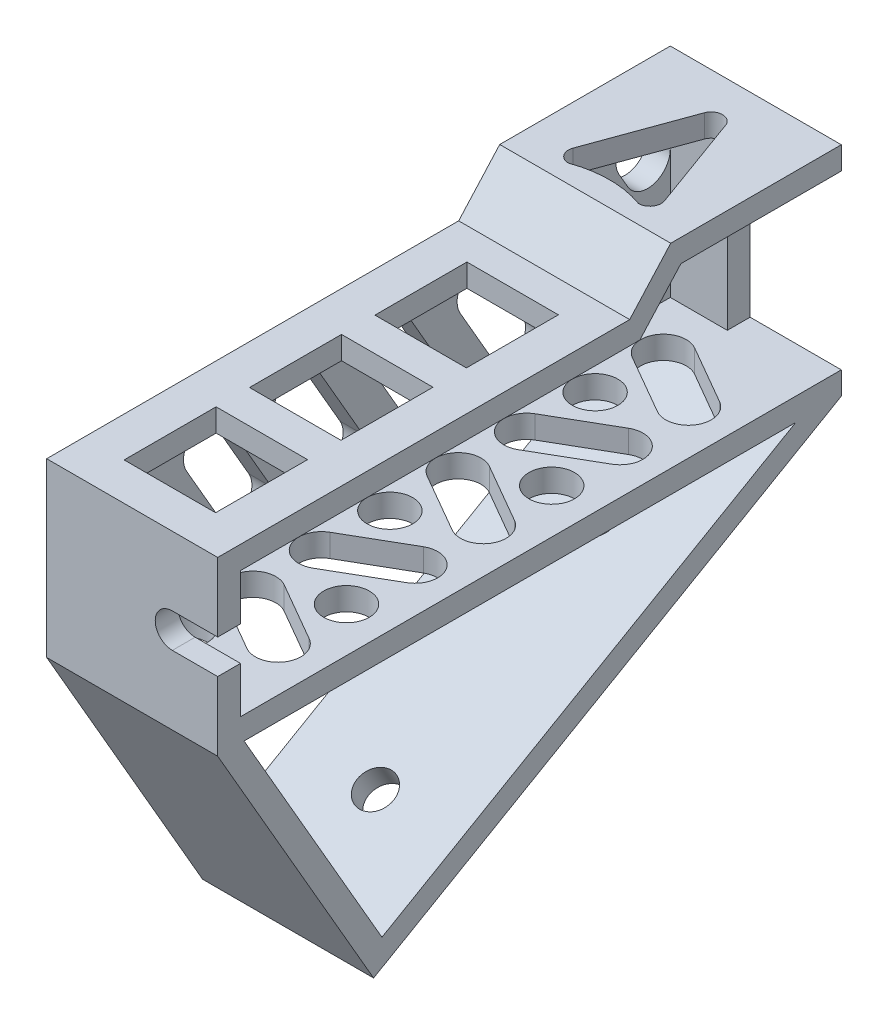
SolidWorks part; units mm, degrees
ref_plane "前视基准面" through (0, 0, 0) normal (0, 0, 1) x (1, 0, 0)
ref_plane "上视基准面" through (0, 0, 0) normal (0, 1, 0) x (1, 0, 0)
ref_plane "右视基准面" through (0, 0, 0) normal (1, 0, 0) x (0, 0, -1)
other "Configuration Table"
sketch "草图1" plane through (0, 0, 0) normal (1, 0, 0) x (0, 0, -1)
  line L0 (13.3, 15) -> (9.7, 11) construction
  line L1 (9.7, 11) -> (-25.3, 11) construction
  line L2 (-25.3, 11) -> (-25.3, 0) construction
  line L3 (-25.3, 0) -> (25.3, 0) construction
  line L4 (25.3, 0) -> (25.3, 15) construction
  line L5 (25.3, 15) -> (13.3, 15) construction
  line L12 (13.2777, 15.05) -> (9.6777, 11.05)
  line L13 (9.6777, 11.05) -> (-25.35, 11.05)
  line L14 (-25.35, 11.05) -> (-25.35, -0.05)
  line L15 (-25.35, -0.05) -> (25.35, -0.05)
  line L16 (25.35, -0.05) -> (25.35, 15.05)
  line L17 (25.35, 15.05) -> (13.2777, 15.05)
  line L18 (12.387, 17.05) -> (8.787, 13.05)
  line L19 (8.787, 13.05) -> (-27.35, 13.05)
  line L20 (-27.35, 13.05) -> (-27.35, -2.05)
  line L21 (-27.35, -2.05) -> (27.35, -2.05)
  line L22 (27.35, -2.05) -> (27.35, 17.05)
  line L23 (27.35, 17.05) -> (12.387, 17.05)
  point P7 (0, 0)
  dimension "D1" = 50.6
  dimension "D2" = 15
  dimension "D3" = 12
  dimension "D4" = 35
  dimension "D5" = 11
  dimension "D6" = 0.05
  dimension "D7" = 2
extrude "凸台-拉伸1" add sketch "草图1" along normal blind 15 contours L16 L17 L12 L13 L14 L15 | L12 L13 L14 L15 L16 L17 | L18 L19 L20 L21 L22 L23 region at (0, 6.1699, -1.6492)
extrude "凸台-拉伸2" add sketch "草图1<3>" along normal blind 2 contours L16 L17 L12 L13 L14 L15 region at (0, 6.1699, -1.6492)
sketch "草图1<3>" plane through (0, 0, 0) normal (1, 0, 0) x (0, 0, -1) same geometry as "草图1"
sketch "草图2" plane through (0, 0, 27.35) normal (0, 0, 1) x (1, 0, 0)
  line L0 (0, 5.5) -> (15, 5.5) construction
  line L1 (11.02, 7) -> (15, 7)
  line L2 (11.02, 4) -> (15, 4)
  line L4 (0, 13.05) -> (0, -2.05)
  line L5 (0, -2.05) -> (15, -2.05)
  line L6 (15, -2.05) -> (15, 13.05)
  line L7 (15, 13.05) -> (0, 13.05)
  line L8 (0, 13.05) -> (0, -2.05) construction
  line L9 (0, -2.05) -> (15, -2.05) construction
  line L10 (15, -2.05) -> (15, 13.05) construction
  line L11 (15, 13.05) -> (0, 13.05) construction
  circle A0 centre (11.02, 5.5) radius 1.5
  line M8 (15, -2.05) -> (15, 13.05)
  dimension "D2" = 3
  dimension "D3" = 11.02
  dimension "D1" = 0
extrude "切除-拉伸1" cut sketch "草图2" against normal up to next contours A0 | A0 L2 L1 M8 region at (13.579, 5.5, 27.35) region at (11.02, 5.5, 27.35)
sketch "草图3" plane through (0, 0, 0) normal (1, 0, 0) x (0, 0, -1)
  line L0 (27.35, -2.05) -> (-27.35, -2.05)
  line L2 (-13.675, -25.7358) -> (27.35, -2.05)
  line L3 (-12.9429, -23.0037) -> (23.35, -2.05)
  line L6 (-27.35, -2.05) -> (-13.675, -25.7358)
  line L7 (-25.0406, -2.05) -> (-12.9429, -23.0037)
  dimension "D1" = 30
  dimension "D2" = 2
  dimension "D3" = 2
extrude "凸台-拉伸3" add sketch "草图3" along normal blind 15 contours L0 L2 L3 region at (0, -13.3767, -6.5395)
sketch "草图4" plane through (0, 0, -27.35) normal (0, 0, -1) x (-1, 0, 0)
  line L0 (-7, 17.05) -> (-7, -2.05) construction
  line L2 (-15, 15.05) -> (-7, 15.05)
  line L3 (-15, 15.05) -> (-15, -0.05)
  line L4 (0, -2.05) -> (0, 17.05)
  line L5 (0, 17.05) -> (-15, 17.05)
  line L6 (-15, 17.05) -> (-15, -2.05)
  line L7 (-15, -2.05) -> (0, -2.05)
  line L8 (0, -2.05) -> (0, 17.05) construction
  line L9 (0, 17.05) -> (-15, 17.05) construction
  line L10 (-15, 17.05) -> (-15, -2.05) construction
  line L11 (-15, -2.05) -> (0, -2.05) construction
  line L12 (-15, -0.05) -> (-7, -0.05)
  line L13 (-7, 15.05) -> (-7, -0.05)
  line L14 (-15, 15.05) -> (-7, -0.05) construction
  line L15 (-15, -0.05) -> (-7, 15.05) construction
  point P10 (-11, 7.5)
  dimension "D2" = 7
  dimension "D3" = 2
  dimension "D4" = 2
  dimension "D1" = 0
extrude "切除-拉伸2" cut sketch "草图4" against normal up to next
sketch "草图5" plane through (0, -13.3804, -7.7252) normal (0, -0.866, -0.5) x (1, 0, 0)
  line L0 (7.5, 24.7108) -> (7.5, -22.6608) construction
  line L4 (0, 24.7108) -> (0, -22.6608)
  line L5 (0, -22.6608) -> (15, -22.6608)
  line L6 (15, -22.6608) -> (15, 24.7108)
  line L7 (15, 24.7108) -> (0, 24.7108)
  line L8 (0, 24.7108) -> (0, -22.6608) construction
  line L9 (0, -22.6608) -> (15, -22.6608) construction
  line L10 (15, -22.6608) -> (15, 24.7108) construction
  line L11 (15, 24.7108) -> (0, 24.7108) construction
  circle A0 centre (7.5, 14.7108) radius 1.6
  circle A1 centre (7.5, -7.6608) radius 1.6
  dimension "D2" = 3.2
  dimension "D4" = 3.2
  dimension "D3" = 10
  dimension "D5" = 15
  dimension "D1" = 0
extrude "切除-拉伸3" cut sketch "草图5" against normal up to next
sketch "草图6" plane through (0, 0, 0) normal (1, 0, 0) x (0, 0, -1)
  line L0 (-27.35, 5.5) -> (27.35, 5.5) construction
  line L1 (-23.35, 8.9641) -> (-19.35, 2.0359) construction
  line L2 (-21.6179, 9.9641) -> (-17.6179, 3.0359)
  line L3 (-25.0821, 7.9641) -> (-21.0821, 1.0359)
  line L4 (-15.35, 8.9641) -> (-11.35, 2.0359) construction
  line L5 (-13.6179, 9.9641) -> (-9.6179, 3.0359)
  line L6 (-17.0821, 7.9641) -> (-13.0821, 1.0359)
  line L7 (-7.35, 8.9641) -> (-3.35, 2.0359) construction
  line L8 (-5.6179, 9.9641) -> (-1.6179, 3.0359)
  line L9 (-9.0821, 7.9641) -> (-5.0821, 1.0359)
  line L10 (0.65, 8.9641) -> (4.65, 2.0359) construction
  line L11 (2.3821, 9.9641) -> (6.3821, 3.0359)
  line L12 (-1.0821, 7.9641) -> (2.9179, 1.0359)
  line L13 (8.65, 8.9641) -> (12.65, 2.0359) construction
  line L14 (10.3821, 9.9641) -> (14.3821, 3.0359)
  line L15 (6.9179, 7.9641) -> (10.9179, 1.0359)
  line L16 (14.5797, 12.55) -> (20.65, 2.0359) construction
  line L17 (16.3117, 13.55) -> (22.3821, 3.0359)
  line L18 (12.8476, 11.55) -> (18.9179, 1.0359)
  line L19 (22.5797, 12.55) -> (23.35, 11.2158) construction
  line L20 (24.3117, 13.55) -> (25.0821, 12.2158)
  line L21 (20.8476, 11.55) -> (21.6179, 10.2158)
  arc A0 (-21.6179, 9.9641) -> (-25.0821, 7.9641) centre (-23.35, 8.9641) ccw
  arc A1 (-21.0821, 1.0359) -> (-17.6179, 3.0359) centre (-19.35, 2.0359) ccw
  arc A2 (-13.6179, 9.9641) -> (-17.0821, 7.9641) centre (-15.35, 8.9641) ccw
  arc A3 (-13.0821, 1.0359) -> (-9.6179, 3.0359) centre (-11.35, 2.0359) ccw
  arc A4 (-5.6179, 9.9641) -> (-9.0821, 7.9641) centre (-7.35, 8.9641) ccw
  arc A5 (-5.0821, 1.0359) -> (-1.6179, 3.0359) centre (-3.35, 2.0359) ccw
  arc A6 (2.3821, 9.9641) -> (-1.0821, 7.9641) centre (0.65, 8.9641) ccw
  arc A7 (2.9179, 1.0359) -> (6.3821, 3.0359) centre (4.65, 2.0359) ccw
  arc A8 (10.3821, 9.9641) -> (6.9179, 7.9641) centre (8.65, 8.9641) ccw
  arc A9 (10.9179, 1.0359) -> (14.3821, 3.0359) centre (12.65, 2.0359) ccw
  arc A10 (16.3117, 13.55) -> (12.8476, 11.55) centre (14.5797, 12.55) ccw
  arc A11 (18.9179, 1.0359) -> (22.3821, 3.0359) centre (20.65, 2.0359) ccw
  arc A12 (24.3117, 13.55) -> (20.8476, 11.55) centre (22.5797, 12.55) ccw
  arc A13 (21.6179, 10.2158) -> (25.0821, 12.2158) centre (23.35, 11.2158) ccw
  point P4 (-21.35, 5.5)
  point P9 (22.9648, 11.8829)
  point P13 (-13.35, 5.5)
  point P20 (-5.35, 5.5)
  point P27 (2.65, 5.5)
  point P34 (10.65, 5.5)
  point P42 (17.6148, 7.2929)
  dimension "D1" = 2
  dimension "D5" = 2
  dimension "D7" = 2
  dimension "D2" = 8
  dimension "D3" = 60
  dimension "D4" = 8
  dimension "D6" = 8
  dimension "D8" = 8
extrude "切除-拉伸5" cut sketch "草图6" along normal up to next contours L21 A13 L20 A12 | L18 A11 L17 A10 | L15 A9 L14 A8 | L12 A7 L11 A6 | L9 A5 L8 A4 | L6 A3 L5 A2 | L3 A1 L2 A0 region at (0, 5.5, 21.35) region at (0, 5.5, 13.35) region at (0, 5.5, 5.35) region at (0, 5.5, -2.65) region at (0, 5.5, -10.65) region at (0, 7.2929, -17.6148) region at (0, 11.8829, -22.9648)
sketch "草图7" plane through (0, 17.05, 0) normal (0, 1, 0) x (1, 0, 0)
  line L0 (7.5, 27.35) -> (7.5, -27.35) construction
  line L1 (3.0002, 13.987) -> (11.9998, 13.987) construction
  line L2 (11.9998, 13.987) -> (7.5, 26.35) construction
  line L3 (7.5, 26.35) -> (3.0002, 13.987) construction
  line L4 (3.4887, 15.329) -> (6.5603, 23.7682)
  line L5 (8.4397, 23.7682) -> (11.5113, 15.329)
  line L6 (10.5716, 13.987) -> (4.4284, 13.987) construction
  line L7 (11.5113, -13.0472) -> (11.5113, -4.9788)
  line L8 (3.4887, -2.0472) -> (11.5113, -2.0472)
  line L9 (3.4887, -2.0472) -> (3.4887, 6.0212)
  line L10 (3.4887, 6.0212) -> (11.5113, 6.0212)
  line L11 (11.5113, -2.0472) -> (11.5113, 6.0212)
  line L12 (3.4887, -2.0472) -> (11.5113, 6.0212) construction
  line L13 (3.4887, 6.0212) -> (11.5113, -2.0472) construction
  line L14 (3.4887, -13.0472) -> (3.4887, -4.9788)
  line L15 (3.4887, -13.0472) -> (11.5113, -13.0472)
  line L16 (3.4887, -4.9788) -> (11.5113, -4.9788)
  line L17 (11.5113, -24.0472) -> (11.5113, -15.9788)
  line L18 (3.4887, -24.0472) -> (3.4887, -15.9788)
  line L19 (3.4887, -24.0472) -> (11.5113, -24.0472)
  line L20 (3.4887, -15.9788) -> (11.5113, -15.9788)
  line L21 (7.5, 27.35) -> (7.5, 26.35) construction
  line L22 (15, 27.35) -> (0, 27.35) construction
  arc A0 (11.5113, 15.329) -> (10.5716, 13.987) centre (10.5716, 14.987) cw
  arc A1 (3.4887, 15.329) -> (4.4284, 13.987) centre (4.4284, 14.987) ccw
  arc A2 (6.5603, 23.7682) -> (8.4397, 23.7682) centre (7.5, 23.4262) cw
  arc A3 (4.4284, 13.987) -> (10.5716, 13.987) centre (7.5, 5.5274) cw
  point P5 (7.5, 13.987)
  point P16 (7.5, 1.987)
  point P29 (3.4887, 1.987)
  point P30 (3.4887, -9.013)
  dimension "D2" = 1
  dimension "D3" = 9
  dimension "D1" = 70
  dimension "D4" = 8.0684
  dimension "D5" = 8.0226
  dimension "D6" = 11
extrude "切除-拉伸6" cut sketch "草图7" against normal up to next
sketch "草图8" plane through (0, -0.05, 0) normal (0, 1, 0) x (1, 0, 0)
  line L0 (5.9019, 20.85) -> (11.0981, 17.85) construction
  line L1 (6.9019, 22.5821) -> (12.0981, 19.5821)
  line L2 (4.9019, 19.1179) -> (10.0981, 16.1179)
  line L3 (5.9019, 8.85) -> (11.0981, 11.85) construction
  line L4 (4.9019, 10.5821) -> (10.0981, 13.5821)
  line L5 (6.9019, 7.1179) -> (12.0981, 10.1179)
  line L6 (15, -25.35) -> (15, 25.35) construction
  line L7 (15, 25.35) -> (10, 25.35) construction
  line L8 (10, 25.35) -> (10, 27.35) construction
  line L9 (10, 27.35) -> (2, 27.35) construction
  line L10 (2, 27.35) -> (2, -25.35) construction
  line L11 (2, -25.35) -> (15, -25.35) construction
  line L12 (8.5, -25.35) -> (8.5, 27.35) construction
  line L13 (5.9019, 2.85) -> (11.0981, -0.15) construction
  line L14 (6.9019, 4.5821) -> (12.0981, 1.5821)
  line L15 (4.9019, 1.1179) -> (10.0981, -1.8821)
  line L16 (5.9019, -9.15) -> (11.0981, -6.15) construction
  line L17 (4.9019, -7.4179) -> (10.0981, -4.4179)
  line L18 (6.9019, -10.8821) -> (12.0981, -7.8821)
  line L19 (5.9019, -15.15) -> (11.0981, -18.15) construction
  line L20 (6.9019, -13.4179) -> (12.0981, -16.4179)
  line L21 (4.9019, -16.8821) -> (10.0981, -19.8821)
  line L22 (2, 14.85) -> (15, 14.85) construction
  line L23 (2, 5.85) -> (15, 5.85) construction
  line L30 (2, 25.35) -> (2, -25.35)
  line L31 (2, -25.35) -> (15, -25.35)
  line L32 (15, -25.35) -> (15, 27.35)
  line L33 (15, 27.35) -> (7, 27.35)
  line L34 (7, 27.35) -> (7, 25.35)
  line L35 (7, 25.35) -> (2, 25.35)
  line L36 (2, 25.35) -> (2, -25.35) construction
  line L37 (2, -25.35) -> (15, -25.35) construction
  line L38 (15, -25.35) -> (15, 27.35) construction
  line L39 (15, 27.35) -> (7, 27.35) construction
  line L40 (7, 27.35) -> (7, 25.35) construction
  line L41 (7, 25.35) -> (2, 25.35) construction
  arc A0 (6.9019, 22.5821) -> (4.9019, 19.1179) centre (5.9019, 20.85) ccw
  arc A1 (10.0981, 16.1179) -> (12.0981, 19.5821) centre (11.0981, 17.85) ccw
  arc A2 (4.9019, 10.5821) -> (6.9019, 7.1179) centre (5.9019, 8.85) ccw
  arc A3 (12.0981, 10.1179) -> (10.0981, 13.5821) centre (11.0981, 11.85) ccw
  arc A4 (6.9019, 4.5821) -> (4.9019, 1.1179) centre (5.9019, 2.85) ccw
  arc A5 (10.0981, -1.8821) -> (12.0981, 1.5821) centre (11.0981, -0.15) ccw
  arc A6 (4.9019, -7.4179) -> (6.9019, -10.8821) centre (5.9019, -9.15) ccw
  arc A7 (12.0981, -7.8821) -> (10.0981, -4.4179) centre (11.0981, -6.15) ccw
  arc A8 (6.9019, -13.4179) -> (4.9019, -16.8821) centre (5.9019, -15.15) ccw
  arc A9 (10.0981, -19.8821) -> (12.0981, -16.4179) centre (11.0981, -18.15) ccw
  circle A10 centre (5.9019, 14.85) radius 2
  circle A11 centre (11.0981, 5.85) radius 2
  circle A12 centre (5.9019, -3.15) radius 2
  circle A13 centre (11.0981, -12.15) radius 2
  circle A14 centre (5.9019, -21.15) radius 2
  point P6 (8.5, 19.35)
  point P15 (8.5, 10.35)
  point P24 (8.5, 1.35)
  point P31 (8.5, -7.65)
  point P38 (8.5, -16.65)
  dimension "D1" = 2
  dimension "D2" = 2
  dimension "D10" = 4
  dimension "D12" = 4
  dimension "D3" = 6
  dimension "D4" = 6
  dimension "D5" = 60
  dimension "D6" = 60
  dimension "D7" = 9
  dimension "D8" = 8
  dimension "D9" = 9
  dimension "D11" = 4.5
  dimension "D13" = 6
  dimension "D14" = 0
extrude "切除-拉伸7" cut sketch "草图8" against normal up to next
